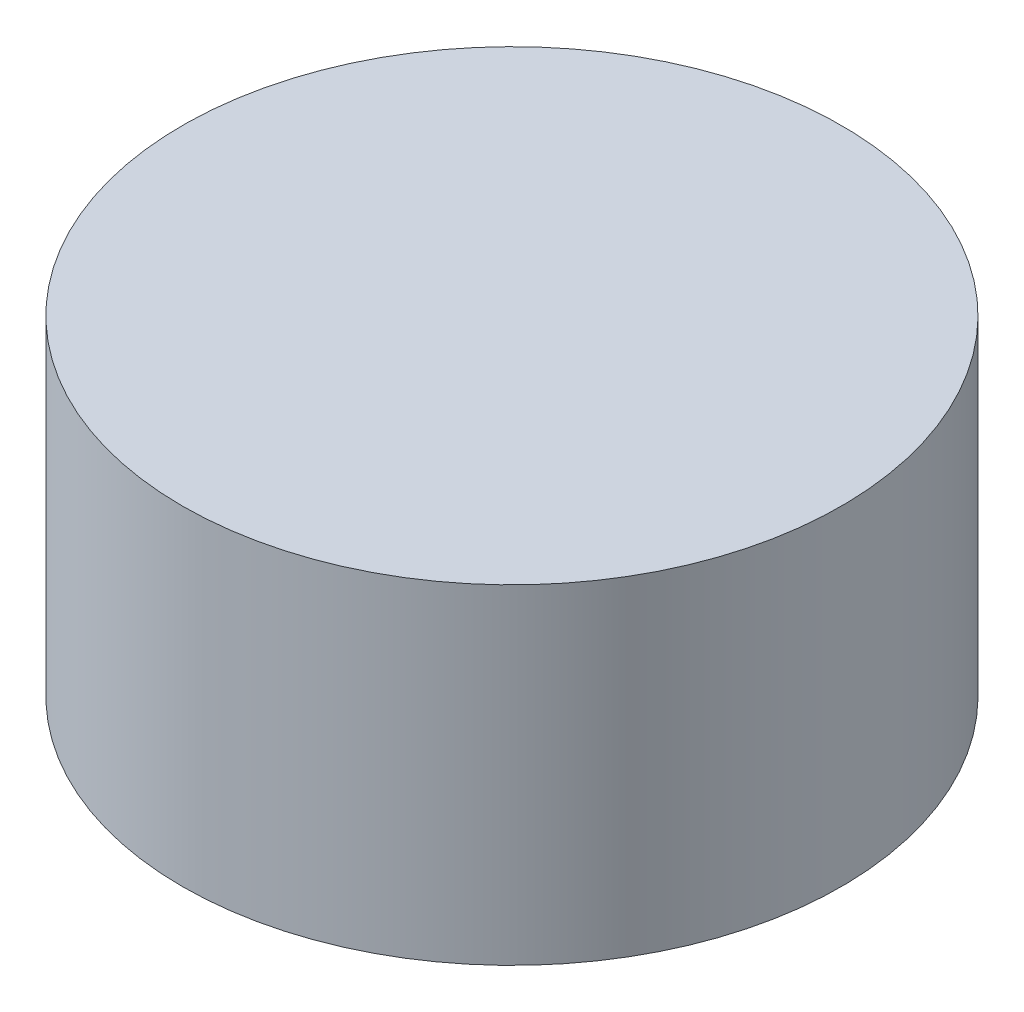
SolidWorks part; units mm, degrees
ref_plane "前视基准面" through (0, 0, 0) normal (0, 0, 1) x (1, 0, 0)
ref_plane "上视基准面" through (0, 0, 0) normal (0, 1, 0) x (1, 0, 0)
ref_plane "右视基准面" through (0, 0, 0) normal (1, 0, 0) x (0, 0, -1)
other "Configuration Table"
sketch "Sketch1" plane through (0, 0, 0) normal (0, 1, 0) x (1, 0, 0)
  circle A0 centre (0, 0) radius 60
extrude "Boss-Extrude1" add sketch "Sketch1" along normal blind 60
sketch3d "3DSketch1"
  line L0 (0, 0, 0) -> (0, 100, 0) construction
ref_axis "Axis_J1" through (0, 0, 0) along (0, 1, 0)
sketch "Sketch2" plane through (0, 0, 0) normal (0, 1, 0) x (1, 0, 0)
  circle A0 centre (0, 0) radius 60
extrude "Boss-Extrude2" add sketch "Sketch2" along normal blind 60
sketch3d "3DSketch2"
  line L0 (0, 0, 0) -> (0, 100, 0) construction
ref_axis "Axis2" through (0, 0, 0) along (0, 1, 0)
ref_plane "Mate_Top" through (0, 60, 0) normal (0, 1, 0) x (1, 0, 0)
